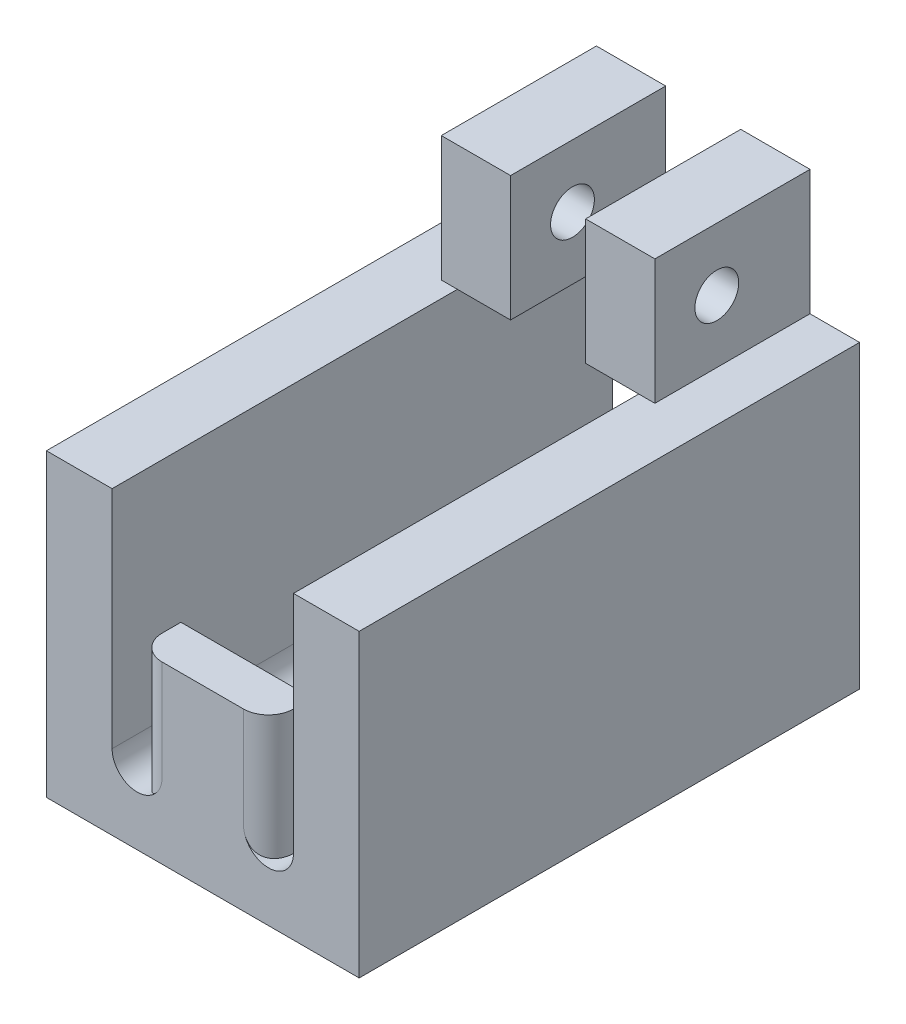
SolidWorks part; units mm, degrees
ref_plane "Front Plane" through (0, 0, 0) normal (0, 0, 1) x (1, 0, 0)
ref_plane "Top Plane" through (0, 0, 0) normal (0, 1, 0) x (1, 0, 0)
ref_plane "Right Plane" through (0, 0, 0) normal (1, 0, 0) x (0, 0, -1)
sketch "Sketch1" plane through (0, 0, 0) normal (0, 1, 0) x (1, 0, 0)
  line L1 (12.5, -20) -> (-12.5, -20)
  line L2 (12.5, -20) -> (12.5, 20)
  line L3 (12.5, 20) -> (-12.5, 20)
  line L4 (-12.5, -20) -> (-12.5, 20)
  line L5 (12.5, -20) -> (-12.5, 20) construction
  line L6 (12.5, 20) -> (-12.5, -20) construction
  point P0 (0, 0)
  dimension "D1" = 25
  dimension "D2" = 40
extrude "Boss-Extrude1" add sketch "Sketch1" along normal blind 4 contours L3 L4 L1 L2
sketch "Sketch2" plane through (0, 4, 0) normal (0, 1, 0) x (1, 0, 0)
  line L0 (12.5, -20) -> (-12.5, -20) construction
  line L1 (-12.5, 20) -> (-7.25, 20)
  line L2 (-12.5, 20) -> (-12.5, -20)
  line L3 (-12.5, -20) -> (-7.25, -20)
  line L4 (-7.25, 20) -> (-7.25, -20)
  dimension "D1" = 5.25
extrude "Boss-Extrude2" add sketch "Sketch2" along normal blind 20
mirror "Mirror1" about plane through (0, 0, 0) normal (1, 0, 0) of "Boss-Extrude2"
fillet "Fillet1" radius 2 2 edges at (7.25, 4, 0) (-7.25, 4, 0)
sketch "Sketch3" plane through (0, 4, 0) normal (0, 1, 0) x (1, 0, 0)
  line L0 (5.25, -20) -> (5.25, 20) construction
  line L1 (-5.25, -20) -> (5.25, -20)
  line L2 (-5.25, -20) -> (-5.25, -16.5)
  line L3 (-5.25, -16.5) -> (5.25, -16.5)
  line L4 (5.25, -20) -> (5.25, -16.5)
  dimension "D1" = 3.5
extrude "Boss-Extrude3" add sketch "Sketch3" along normal blind 10
fillet "Fillet2" radius 2 3 edges at (-5.25, 9, 20) (5.25, 9, 20) (0, 4, 16.5)
ref_plane "Plane1" through (0, 24, 0) normal (0, 1, 0) x (1, 0, 0)
sketch "Sketch4" plane through (0, 24, 0) normal (0, 1, 0) x (1, 0, 0)
  line L0 (0, -13.2) -> (0, 13.2) construction
  line L4 (-3, 20) -> (-3, 7.6016)
  line L5 (8.5368, 7.6016) -> (3, 7.6016)
  line L6 (3, 20) -> (3, 7.6016)
  line L11 (-8.5368, 20) -> (-8.5368, 7.6016)
  line L12 (-8.5368, 20) -> (-3, 20)
  line L13 (-8.5368, 7.6016) -> (-3, 7.6016)
  line L14 (8.5368, 20) -> (3, 20)
  line L15 (8.5368, 20) -> (8.5368, 7.6016)
extrude "Boss-Extrude4" add sketch "Sketch4" along normal blind 10
sketch "Sketch5" plane through (12.5, 0, 0) normal (1, 0, 0) x (0, 0, -1)
  circle A0 centre (12.5508, 29) radius 1.75
  dimension "D1" = 3.5
extrude "Cut-Extrude1" cut sketch "Sketch5" against normal through all
